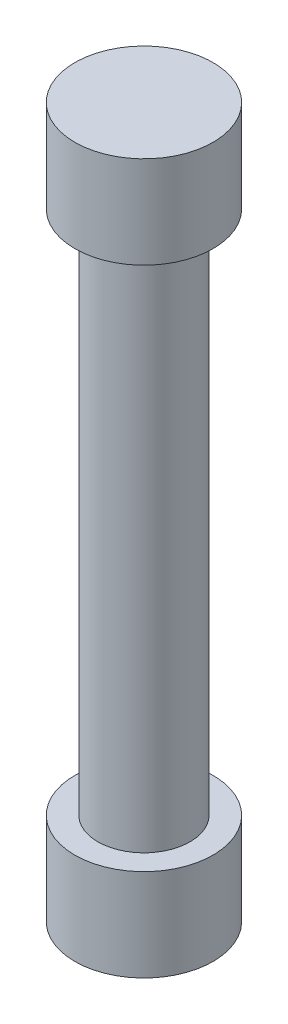
SolidWorks part; units mm, degrees
ref_plane "Front Plane" through (0, 0, 0) normal (0, 0, 1) x (1, 0, 0)
ref_plane "Top Plane" through (0, 0, 0) normal (0, 1, 0) x (1, 0, 0)
ref_plane "Right Plane" through (0, 0, 0) normal (1, 0, 0) x (0, 0, -1)
sketch "Sketch1" plane through (0, 0, 0) normal (0, 1, 0) x (1, 0, 0)
  circle A0 centre (0, 0) radius 1.5
  dimension "D1" = 3
extrude "Boss-Extrude1" add sketch "Sketch1" along normal blind 17.1
sketch "Sketch2" plane through (0, 17.1, 0) normal (0, 1, 0) x (1, 0, 0)
  circle A0 centre (0, 0) radius 2.25
  dimension "D1" = 4.5
extrude "Boss-Extrude2" add sketch "Sketch2" along normal blind 3
extrude "Boss-Extrude3" add sketch "Sketch2<2>" against normal blind 3 from surface starting at face at (0, 0, 1.5)
sketch "Sketch2<2>" plane through (0, 17.1, 0) normal (0, 1, 0) x (1, 0, 0) same geometry as "Sketch2"
